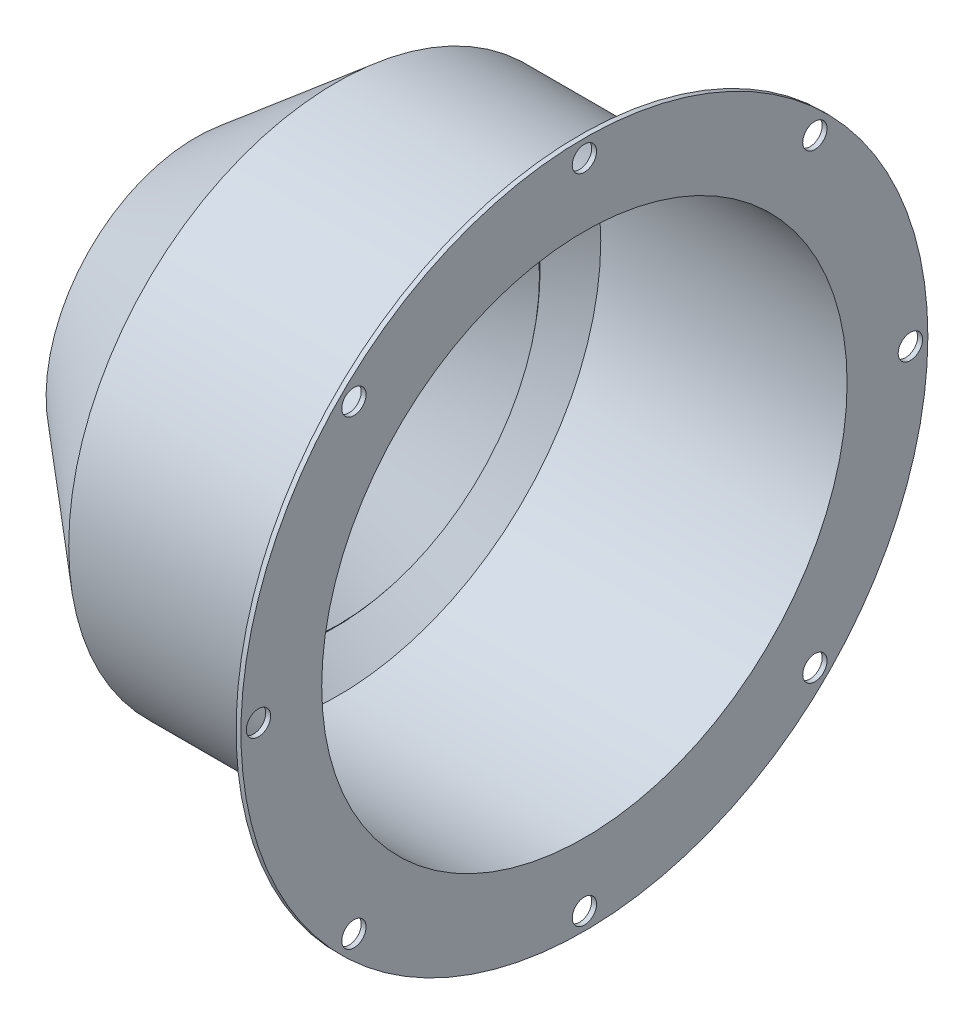
SolidWorks part; units mm, degrees
ref_plane "Front Plane" through (0, 0, 0) normal (0, 0, 1) x (1, 0, 0)
ref_plane "Top Plane" through (0, 0, 0) normal (0, 1, 0) x (1, 0, 0)
ref_plane "Right Plane" through (0, 0, 0) normal (1, 0, 0) x (0, 0, -1)
sketch "Sketch2" plane through (-56.3929, 12.9644, 6.3798) normal (0, 0, -1) x (1, 0, 0)
  line L0 (8.1153, 89.662) -> (8.1153, 68.58)
  line L1 (8.1153, 89.7128) -> (8.1153, -89.7128) construction
  line L2 (8.1153, 89.662) -> (6.8453, 89.662)
  line L3 (6.8453, 89.662) -> (6.8453, 69.85)
  line L4 (8.1153, 76.2) -> (8.1153, -76.2) construction
  line L5 (8.1153, 68.58) -> (-56.1925, 68.58)
  line L6 (-56.1925, 68.58) -> (-92.5171, 38.1)
  line L7 (-92.5171, 38.1) -> (-93.3334, 39.0729)
  line L8 (-93.3334, 39.0729) -> (-56.6547, 69.85)
  line L9 (-56.6547, 69.85) -> (6.8453, 69.85)
  line L10 (41.3304, 0) -> (-77.7743, 0) construction
  line L11 (87.376, 0) -> (4.7958, 0) construction
  dimension "D1" = 21.082
  dimension "D2" = 1.27
  dimension "D3" = 1.27
  dimension "D4" = 89.662
  dimension "D5" = 1.27
  dimension "D6" = 40
  dimension "D7" = 38.1
  dimension "D8" = 63.5
revolve "Revolve1" add sketch "Sketch2" angle 360 about L10
sketch "Sketch4" plane through (88.3744, 12.9644, 6.3798) normal (0, 0, 1) x (1, 0, 0)
  line L0 (-200.9598, 52.578) -> (-263.2659, 0.2969)
  line L2 (-263.2659, 0.2969) -> (-264.0822, 1.2698)
  line L3 (-264.0822, 1.2698) -> (-201.7761, 53.5509)
  line L4 (-201.7761, 53.5509) -> (-200.9598, 52.578)
  line L5 (-166.2127, 0) -> (-290.4908, 0) construction
  dimension "D1" = 1.27
  dimension "D2" = 40
  dimension "D3" = 52.578
revolve "Revolve4" add sketch "Sketch4" angle 360 about L5
sketch "Sketch5" plane through (-49.5476, 0, 0) normal (-1, 0, 0) x (0, 0, 1)
  circle A0 centre (6.3798, 98.0544) radius 3.175
  circle A1 centre (66.5475, 73.1322) radius 3.175
  circle A2 centre (91.4698, 12.9644) radius 3.175
  circle A3 centre (66.5475, -47.2033) radius 3.175
  circle A4 centre (6.3798, -72.1256) radius 3.175
  circle A5 centre (-53.7879, -47.2033) radius 3.175
  circle A6 centre (-78.7102, 12.9644) radius 3.175
  circle A7 centre (-53.7879, 73.1322) radius 3.175
  point P20 (6.3798, 12.9644)
  dimension "D1" = 6.35
  dimension "D2" = 85.09
  dimension "D3" = 8
extrude "Cut-Extrude1" cut sketch "Sketch5" against normal blind 2.54
sketch "Sketch6" plane through (88.3744, 12.9644, 6.3798) normal (0, 0, 1) x (1, 0, 0)
  line L0 (-240.9299, 35.2196) -> (-233.0808, 25.8653)
  line L1 (-233.0808, 25.8653) -> (-223.352, 34.0287)
  line L2 (-223.352, 34.0287) -> (-231.2012, 43.383)
  line L3 (-231.2012, 43.383) -> (-240.9299, 35.2196)
  line L4 (-160.8493, 0) -> (-248.4528, 0) construction
  line L5 (-68.326, 0) -> (-150.9062, 0) construction
  dimension "D1" = 12.7
  dimension "D2" = 40
extrude "Boss-Extrude1" add sketch "Sketch6" along normal mid plane 1.27
pattern_circular "CirPattern1" count 4 over 360 about axis through (-113.0476, 12.9644, 6.3798) along (-1, 0, 0) of "Boss-Extrude1"
